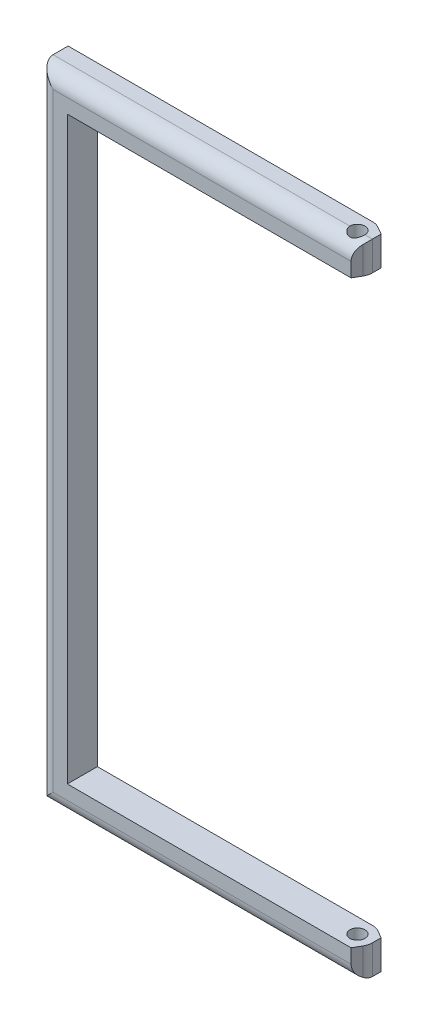
SolidWorks part; units mm, degrees
material "PLA"
ref_plane "前视基准面" through (0, 0, 0) normal (0, 0, 1) x (1, 0, 0)
ref_plane "上视基准面" through (0, 0, 0) normal (0, 1, 0) x (1, 0, 0)
ref_plane "右视基准面" through (0, 0, 0) normal (1, 0, 0) x (0, 0, -1)
sketch "草图1" plane through (0, 0, 0) normal (0, 0, 1) x (1, 0, 0)
  line L8 (136.2994, -68.9419) -> (136.2994, -65.0419)
  line L9 (136.2994, 12.1581) -> (136.2994, 16.0581)
  line L10 (97.6994, 12.1581) -> (136.2994, 12.1581)
  line L11 (97.6994, -65.0419) -> (97.6994, 12.1581)
  line L12 (93.7994, -68.9419) -> (136.2994, -68.9419)
  line L13 (136.2994, -65.0419) -> (97.6994, -65.0419)
  line L14 (93.7994, 16.0581) -> (93.7994, -68.9419)
  line L15 (136.2994, 16.0581) -> (93.7994, 16.0581)
  dimension "D1" = 3.9
  dimension "D2" = 3.9
  dimension "D3" = 3.9
  dimension "D4" = 42.5
extrude "凸台-拉伸1" add sketch "草图1" against normal blind 4
sketch "草图2" plane through (0, -68.9419, 0) normal (0, -1, 0) x (1, 0, 0)
  line L0 (136.2994, -4) -> (136.2994, 0) construction
  line L1 (136.2994, -4) -> (93.7994, -4) construction
  circle A0 centre (134.2994, -2) radius 1
  dimension "D1" = 2
  dimension "D2" = 2
  dimension "D3" = 2
extrude "切除-拉伸1" cut sketch "草图2" against normal up to next
ref_plane "基准面4" through (0, -26.4419, 0) normal (0, -1, 0) x (-1, 0, 0)
mirror "镜向1" about plane through (0, -26.4419, 0) normal (0, -1, 0) of "切除-拉伸1"
sketch "草图3" plane through (0, 16.0581, 0) normal (0, 1, 0) x (1, 0, 0)
  line L0 (136.2994, 3.1547) -> (136.2994, 4)
  line L1 (135.4541, 0) -> (136.0314, 1)
  line L2 (136.2994, 4) -> (93.7994, 4) construction
  line L6 (136.2994, 1.4641) -> (136.2994, 0)
  line L15 (136.2994, 4) -> (136.2994, 0) construction
  line L16 (136.2994, 4) -> (134.2994, 4)
  line L17 (135.2994, 3.7321) -> (136.2994, 3.1547)
  line L19 (136.2994, 0) -> (135.4541, 0)
  line L20 (136.2994, 0) -> (93.7994, 0) construction
  line L21 (136.2994, 1.4641) -> (136.2994, 2)
  arc A0 (134.2994, 4) -> (135.2994, 3.7321) centre (134.2994, 2) cw
  arc A1 (136.0314, 1) -> (136.2994, 2) centre (134.2994, 2) ccw
extrude "切除-拉伸2" cut sketch "草图3" against normal through all and the other way through all
fillet "圆角1" radius 2 3 edges at (114.6267, 16.0581, 0) (93.7994, -26.4419, 0) (114.6267, -68.9419, 0)
